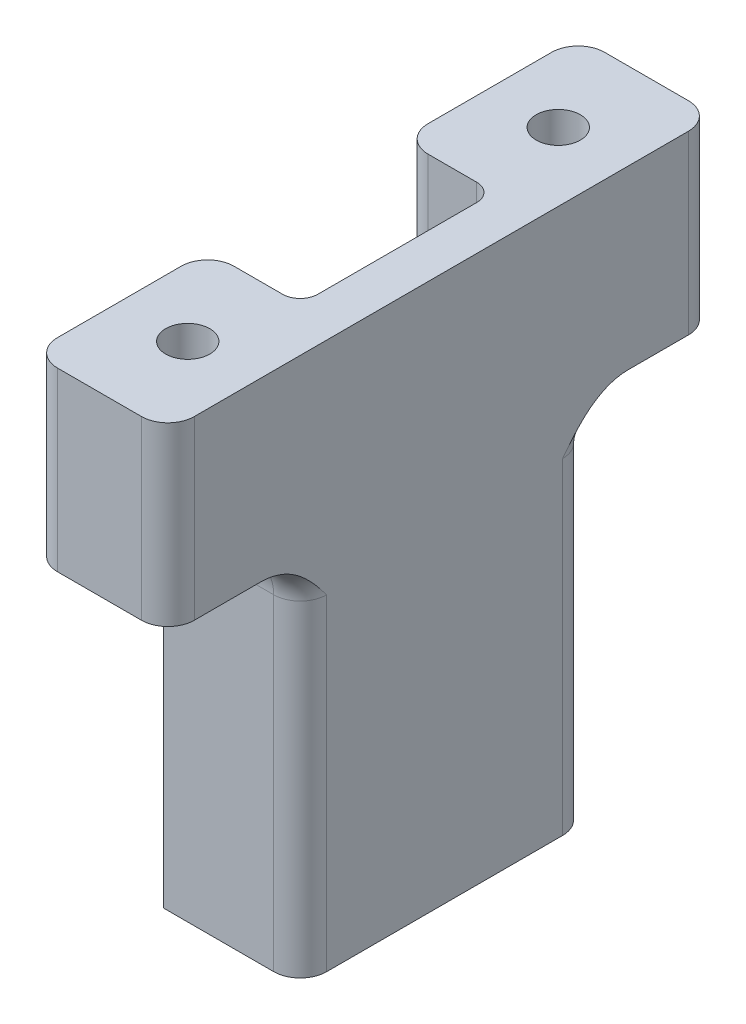
SolidWorks part; units mm, degrees
material "K110"
ref_plane "Front Plane" through (0, 0, 0) normal (0, 0, 1) x (1, 0, 0)
ref_plane "Top Plane" through (0, 0, 0) normal (0, 1, 0) x (1, 0, 0)
ref_plane "Right Plane" through (0, 0, 0) normal (1, 0, 0) x (0, 0, -1)
sketch "Sketch1" plane through (0, 0, 0) normal (0, 1, 0) x (1, 0, 0)
  line L0 (4.37, 30.63) -> (-5.13, 30.63) construction
  line L1 (-8.13, -31.37) -> (7.37, -31.37)
  line L2 (-8.13, -31.37) -> (-8.13, 30.63)
  line L3 (-8.13, 30.63) -> (7.37, 30.63)
  line L4 (7.37, -31.37) -> (7.37, 30.63)
  line L5 (-8.13, 27.63) -> (-8.13, 13.63) construction
  line L6 (7.37, -28.37) -> (7.37, 27.63) construction
  line L7 (-5.13, -31.37) -> (4.37, -31.37) construction
  point P0 (0, 0)
extrude "Boss-Extrude1" add sketch "Sketch1" against normal blind 62
fillet "Fillet1" radius 3 4 edges at (-8.13, -31, -30.63) (7.37, -31, -30.63) (-8.13, -31, 31.37) (7.37, -31, 31.37)
sketch "Sketch2" plane through (0, 0, 0) normal (0, 1, 0) x (1, 0, 0)
  line L0 (-5.13, 10.63) -> (0.37, 10.63) construction
  line L1 (2.37, 8.63) -> (2.37, -9.37) construction
  line L2 (0.37, -11.37) -> (-5.13, -11.37) construction
  line L3 (-5.13, 10.63) -> (0.37, 10.63)
  line L4 (2.37, 8.63) -> (2.37, -9.37)
  line L5 (0.37, -11.37) -> (-5.13, -11.37)
  line L6 (-8.13, 13.63) -> (-8.13, -14.37)
  arc A0 (-8.13, 13.63) -> (-5.13, 10.63) centre (-5.13, 13.63) ccw construction
  arc A1 (2.37, 8.63) -> (0.37, 10.63) centre (0.37, 8.63) ccw construction
  arc A2 (0.37, -11.37) -> (2.37, -9.37) centre (0.37, -9.37) ccw construction
  arc A3 (-5.13, -11.37) -> (-8.13, -14.37) centre (-5.13, -14.37) ccw construction
  arc A4 (-8.13, 13.63) -> (-5.13, 10.63) centre (-5.13, 13.63) ccw
  arc A5 (2.37, 8.63) -> (0.37, 10.63) centre (0.37, 8.63) ccw
  arc A6 (0.37, -11.37) -> (2.37, -9.37) centre (0.37, -9.37) ccw
  arc A7 (-5.13, -11.37) -> (-8.13, -14.37) centre (-5.13, -14.37) ccw
extrude "Cut-Extrude1" cut sketch "Sketch2" against normal up to next
sketch "Sketch3" plane through (0, -62, 0) normal (0, 1, 0) x (1, 0, 0)
  line L1 (-5.13, -31.37) -> (4.37, -31.37) construction
  line L2 (7.37, -28.37) -> (7.37, 27.63) construction
  line L3 (-8.13, -14.37) -> (-8.13, -28.37) construction
  line L4 (4.37, -16.37) -> (-8.13, -16.37) construction
  line L5 (4.37, -16.37) -> (-8.13, -16.37)
  line L6 (-8.13, -16.37) -> (-8.13, -28.37)
  line L7 (7.37, -28.37) -> (7.37, -13.37)
  line L8 (-5.13, -31.37) -> (4.37, -31.37)
  arc A0 (-8.13, -28.37) -> (-5.13, -31.37) centre (-5.13, -28.37) ccw construction
  arc A1 (4.37, -31.37) -> (7.37, -28.37) centre (4.37, -28.37) ccw construction
  arc A2 (4.37, -16.37) -> (7.37, -13.37) centre (4.37, -13.37) ccw construction
  arc A3 (4.37, -16.37) -> (7.37, -13.37) centre (4.37, -13.37) ccw
  arc A4 (4.37, -31.37) -> (7.37, -28.37) centre (4.37, -28.37) ccw
  arc A5 (-8.13, -28.37) -> (-5.13, -31.37) centre (-5.13, -28.37) ccw
extrude "Cut-Extrude2" cut sketch "Sketch3" along normal up to surface (42 mm away)
mirror "Mirror1" about plane through (0, 0, 0) normal (0, 0, 1) of "Cut-Extrude2"
fillet "Fillet2" radius 5 4 edges at (6.4913, -20, -15.4913) (6.4913, -20, 15.4913) (-1.88, -20, -16.37) (-1.88, -20, 16.37)
hole_wizard "M6 Tapped Hole1" positions "Sketch6" profile "Sketch5" tap size "M6" standard "ISO"
sketch "Sketch6" plane through (0, 0, 0) normal (0, 1, 0) x (1, 0, 0)
  line L0 (-0.38, 30.63) -> (-0.38, 10.63) construction
  line L1 (4.37, 30.63) -> (-5.13, 30.63) construction
  line L2 (0.37, 10.63) -> (-5.13, 10.63) construction
  line L4 (-0.38, -31.37) -> (-0.38, -11.37) construction
  line L5 (-5.13, -31.37) -> (4.37, -31.37) construction
  line L6 (-5.13, -11.37) -> (0.37, -11.37) construction
  point P0 (-0.38, 20.63)
  point P2 (-0.38, -21.37)
sketch "Sketch5" plane through (-0.38, 0, -20.63) normal (1, 0, 0) x (0, 0, 1)
  line L0 (0, 0) -> (0, 16.5022)
  line L1 (0, 16.5022) -> (2.5, 15)
  line L2 (2.5, 15) -> (2.5, 0)
  line L5 (2.5, 0) -> (0, 0)
  line L10 (0, 16.5022) -> (-2.5, 15) construction
  line L11 (0, -6.35) -> (0, 107.95) construction
  dimension "Tap Drill Dia." = 5
  dimension "Tap Drill Depth" = 15
  dimension "Drill Angle" = 118
cosmetic thread "Hole Thread1"
cosmetic thread "Hole Thread2"
